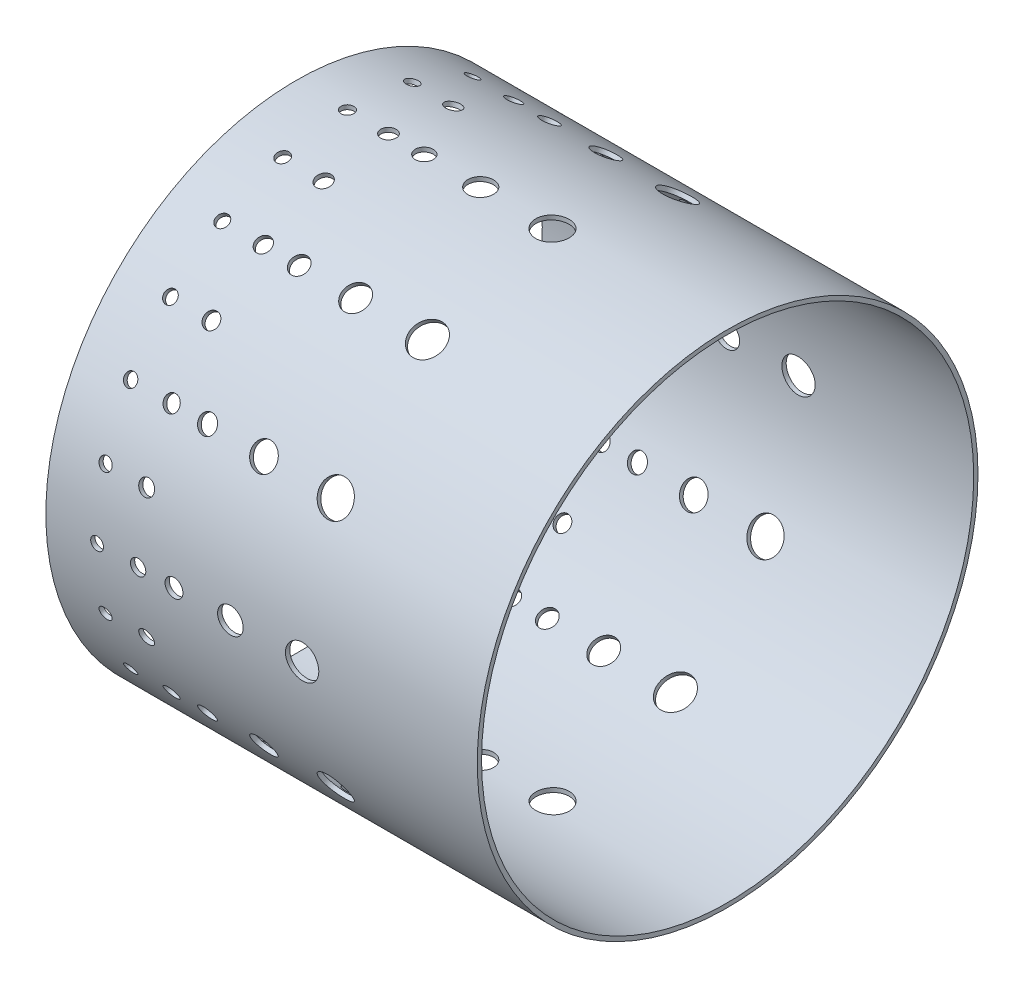
SolidWorks part; units mm, degrees
material "201 Annealed Stainless Steel (SS)"
ref_plane "Front Plane" through (0, 0, 0) normal (0, 0, 1) x (1, 0, 0)
ref_plane "Top Plane" through (0, 0, 0) normal (0, 1, 0) x (1, 0, 0)
ref_plane "Right Plane" through (0, 0, 0) normal (1, 0, 0) x (0, 0, -1)
sketch "Sketch1" plane through (0, 0, 0) normal (1, 0, 0) x (0, 0, -1)
  circle A0 centre (0, 0) radius 48.8442
  circle A1 centre (0, 0) radius 48.006
  dimension "D1" = 0.8382
  dimension "D2" = 96.012
extrude "Boss-Extrude1" add sketch "Sketch1" along normal blind 84.1681
sketch "Sketch3" plane through (0, 0, 0) normal (0, 1, 0) x (1, 0, 0)
  line L0 (0, 0) -> (118.8164, 0) construction
  line L1 (0, 48.8442) -> (0, -48.8442) construction
sketch "Sketch2" plane through (0, 0, 0) normal (0, 1, 0) x (1, 0, 0)
  line L0 (0, 0) -> (89.7894, 0) construction
  line L1 (0, 48.8442) -> (0, -48.8442) construction
  circle A0 centre (10, 0) radius 1.25
  dimension "D2" = 2.5
  dimension "D1" = 10
extrude "Cut-Extrude1" cut sketch "Sketch2" against normal through all
pattern_circular "CirPattern1" count 24 over 360 about axis through (0, 0, 0) along (1, 0, 0) of "Cut-Extrude1"
sketch "Sketch4" plane through (0, 0, 0) normal (0, 0, 1) x (1, 0, 0)
  line L0 (0, 0) -> (118.8164, 0) construction
  circle A0 centre (18, 0) radius 1.5
  dimension "D1" = 18
  dimension "D2" = 3
extrude "Cut-Extrude2" cut sketch "Sketch4" against normal through all
pattern_circular "CirPattern2" count 24 over 360 about axis through (0, 0, 0) along (1, 0, 0) of "Cut-Extrude2" reverse direction yes
sketch "Sketch5" plane through (0, 0, 0) normal (0, 0, 1) x (1, 0, 0)
  line L0 (0, 0) -> (118.8164, 0) construction
  line L1 (0, 48.8442) -> (0, -48.8442) construction
  circle A0 centre (25, 0) radius 1.75
  dimension "D2" = 3.5
  dimension "D1" = 25
extrude "Cut-Extrude3" cut sketch "Sketch5" against normal through all
pattern_circular "CirPattern3" count 12 over 360 about axis through (0, 0, 0) along (1, 0, 0) of "Cut-Extrude3"
sketch "Sketch6" plane through (0, 0, 0) normal (0, 0, 1) x (1, 0, 0)
  line L0 (0, 0) -> (118.8164, 0) construction
  line L1 (0, 48.8442) -> (0, -48.8442) construction
  circle A0 centre (36, 0) radius 2.5
  dimension "D2" = 5
  dimension "D1" = 36
extrude "Cut-Extrude4" cut sketch "Sketch6" against normal through all
pattern_circular "CirPattern4" count 12 over 360 about axis through (0, 0, 0) along (1, 0, 0) of "Cut-Extrude4"
sketch "Sketch7" plane through (0, 0, 0) normal (0, 1, 0) x (1, 0, 0)
  line L0 (0, 0) -> (118.8164, 0) construction
  circle A0 centre (50, 0) radius 3.25
  dimension "D1" = 50
  dimension "D2" = 6.5
extrude "Cut-Extrude5" cut sketch "Sketch7" against normal through all
pattern_circular "CirPattern5" count 12 over 360 about axis through (84.1681, 0, 0) along (-1, 0, 0) of "Cut-Extrude5"
